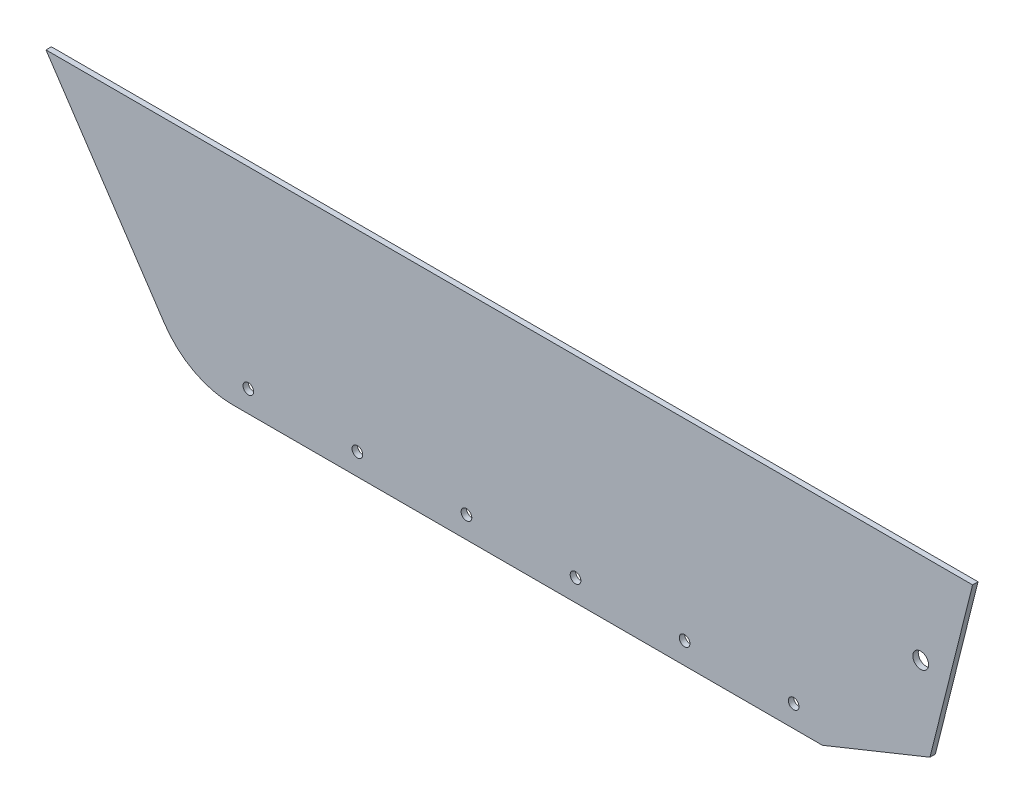
SolidWorks part; units mm, degrees
material "5052-H34"
ref_plane "Front Plane" through (0, 0, 0) normal (0, 0, 1) x (1, 0, 0)
ref_plane "Top Plane" through (0, 0, 0) normal (0, 1, 0) x (1, 0, 0)
ref_plane "Right Plane" through (0, 0, 0) normal (1, 0, 0) x (0, 0, -1)
sketch "Sketch1" plane through (0, 0, 0) normal (0, 0, 1) x (1, 0, 0)
  line L6 (-98.8794, 3.851) -> (-31.8794, -96.649)
  line L7 (428.1206, 28.9396) -> (403.1206, -71.149)
  line L9 (403.1206, -71.149) -> (366, -96.649)
  line L10 (-31.8794, -96.649) -> (366, -96.649)
  line L12 (-98.8794, 3.851) -> (-115.6052, 28.9396)
  line L13 (-115.6052, 28.9396) -> (428.1206, 28.9396)
  circle A0 centre (3.1206, -83.899) radius 3.125
  circle A1 centre (67.1206, -83.899) radius 3.125
  circle A2 centre (131.1206, -83.899) radius 3.125
  circle A3 centre (195.1206, -83.899) radius 3.125
  circle A4 centre (259.1206, -83.899) radius 3.125
  circle A5 centre (323.1206, -83.899) radius 3.125
  point P0 (-48.8794, -71.149)
  point P2 (-31.8794, -96.649)
  point P8 (48, -83.899)
  point P9 (403.1206, -71.149)
  dimension "D2" = 64
  dimension "D4" = 64
  dimension "D14" = 6.25
  dimension "D1" = 25.5
  dimension "D3" = 75
  dimension "D5" = 25
  dimension "D6" = 80
  dimension "D7" = 527
  dimension "D8" = 180
  dimension "D9" = 64
  dimension "D10" = 64
  dimension "D11" = 64
  dimension "D12" = 123.69
  dimension "D13" = 12.75
  dimension "D15" = 366
  dimension "D16" = 115.6052
extrude "Boss-Extrude1" add sketch "Sketch1" along normal blind 3.175 contours L12 L13 L7 L9 L10 L6
extrude "Cut-Extrude1" cut sketch "Sketch1<4>" along normal through all contours A0 | A1 | A2 | A3 | A4 | A5 region at (3.1206, -83.899, 0)
sketch "Sketch1<4>" plane through (0, 0, 0) normal (0, 0, 1) x (1, 0, 0) same geometry as "Sketch1"
sketch "Sketch5" plane through (0, 0, 0) normal (0, 0, -1) x (-1, 0, 0)
  line L0 (48.8794, -71.149) -> (-14.2353, -96.649)
  line L1 (31.8794, -96.649) -> (-366, -96.649) construction
  line L2 (-14.2353, -96.649) -> (31.8794, -96.649)
  line L3 (31.8794, -96.649) -> (48.8794, -71.149)
  line L6 (-366, -96.649) -> (-403.1206, -71.149)
  line L7 (-403.1206, -71.149) -> (-352, -71.149)
  line L9 (-352, -71.149) -> (-326.5, -96.649)
  line L11 (-366, -96.649) -> (-326.5, -96.649)
  dimension "D1" = 22
  dimension "D2" = 45
extrude "Cut-Extrude2" [suppressed] cut sketch "Sketch5" against normal up to next
sketch "Sketch6" plane through (0, 0, 3.175) normal (0, 0, 1) x (1, 0, 0)
  line L0 (-48.8794, -71.149) -> (14.2353, -96.649)
  line L1 (-31.8794, -96.649) -> (366, -96.649) construction
  line L2 (14.2353, -96.649) -> (-31.8794, -96.649)
  line L3 (-31.8794, -96.649) -> (-48.8794, -71.149)
  dimension "D1" = 158
fillet "Fillet1" radius 48 1 edges at (-31.8794, -96.649, 1.5875)
sketch "Sketch7" plane through (0, 0, 3.175) normal (0, 0, 1) x (1, 0, 0)
  line L0 (403.1206, -71.149) -> (340.0059, -96.649)
  line L1 (-31.8794, -96.649) -> (366, -96.649) construction
  line L2 (340.0059, -96.649) -> (366, -96.649)
  line L3 (366, -96.649) -> (403.1206, -71.149)
  dimension "D1" = 22
extrude "Cut-Extrude3" cut sketch "Sketch7" against normal blind 10
sketch "Sketch9" plane through (0, 0, 0) normal (0, 0, -1) x (-1, 0, 0)
  line L0 (-403.1206, -71.149) -> (48.8794, -71.149)
  line L1 (48.8794, -71.149) -> (48.8794, -114.9143)
  line L2 (48.8794, -114.9143) -> (-403.1206, -114.9143)
  line L3 (-403.1206, -114.9143) -> (-403.1206, -71.149)
sketch "Sketch11" plane through (0, 0, 0) normal (0, 0, -1) x (-1, 0, 0)
  circle A0 centre (-397.6786, -24.6104) radius 4.625
  dimension "D1" = 9.25
extrude "Cut-Extrude5" cut sketch "Sketch11" against normal up to next
sketch "Sketch12" plane through (0, 0, 3.175) normal (0, 0, 1) x (1, 0, 0)
  line L1 (875.2623, -24.6104) -> (-79.9052, -24.6104)
  line L2 (-115.6052, 28.9396) -> (-46.129, -75.2746) construction
  line L3 (-6.1906, -96.649) -> (340.0059, -96.649) construction
  circle A0 centre (397.6786, -24.6104) radius 4.625 construction
  circle A1 centre (397.6786, -24.6104) radius 4.625
  point P8 (397.6786, -24.6104)
  point P10 (-64.9052, -24.6104)
  dimension "D1" = 15
